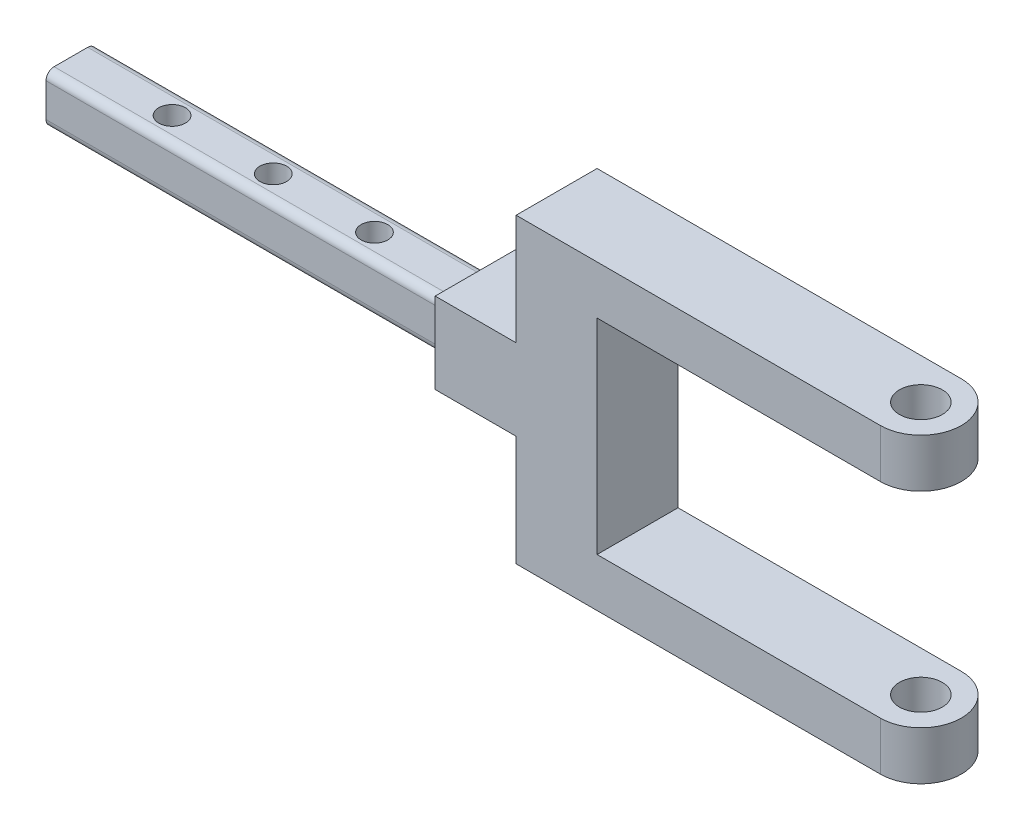
SolidWorks part; units mm, degrees
ref_plane "前视基准面" through (0, 0, 0) normal (0, 0, 1) x (1, 0, 0)
ref_plane "上视基准面" through (0, 0, 0) normal (0, 1, 0) x (1, 0, 0)
ref_plane "右视基准面" through (0, 0, 0) normal (1, 0, 0) x (0, 0, -1)
other "Configuration Table"
sketch "草图1" plane through (0, 0, 0) normal (0, 0, 1) x (1, 0, 0)
  line L0 (0, 12.65) -> (0, -12.65)
  line L1 (0, 12.65) -> (40, 12.65)
  line L2 (40, 12.65) -> (40, 18.65)
  line L3 (40, 18.65) -> (-10, 18.65)
  line L4 (-10, 18.65) -> (-10, -18.65)
  line L5 (-10, -18.65) -> (40, -18.65)
  line L6 (40, -18.65) -> (40, -12.65)
  line L7 (40, -12.65) -> (0, -12.65)
  point P4 (0, 0)
  dimension "D1" = 25.3
  dimension "D2" = 40
  dimension "D3" = 6
  dimension "D4" = 10
extrude "凸台-拉伸1" add sketch "草图1" along normal blind 10
sketch "草图2" plane through (-10, 0, 0) normal (-1, 0, 0) x (0, 0, 1)
  line L0 (8.075, 3.075) -> (8.075, -3.075)
  line L1 (1.925, -3.075) -> (8.075, -3.075)
  line L2 (1.925, 3.075) -> (1.925, -3.075)
  line L3 (1.925, 3.075) -> (8.075, 3.075)
  line L4 (5, 18.65) -> (5, -18.65) construction
  line L5 (0, 0) -> (10, 0) construction
  line L7 (0, 5) -> (10, 5)
  line L8 (0, 18.65) -> (0, -18.65)
  line L9 (0, -18.65) -> (10, -18.65)
  line L10 (10, -18.65) -> (10, 18.65)
  line L11 (10, 18.65) -> (0, 18.65)
  line L12 (0, 18.65) -> (0, -18.65)
  line L13 (0, -18.65) -> (10, -18.65)
  line L14 (10, -18.65) -> (10, 18.65)
  line L15 (10, 18.65) -> (0, 18.65)
  line L16 (0, 5) -> (0, -5)
  line L17 (0, -5) -> (10, -5)
  line L18 (10, 5) -> (10, -5)
  line L19 (5, -5) -> (5, 5) construction
  line L20 (0, 0) -> (10, 0) construction
  line L21 (1.5, 3.5) -> (8.5, 3.5) construction
  line L22 (1.5, 3.5) -> (1.5, -3.5) construction
  line L23 (1.5, -3.5) -> (8.5, -3.5) construction
  line L24 (8.5, 3.5) -> (8.5, -3.5) construction
  line L25 (5, -3.5) -> (5, 3.5) construction
  line L26 (1.5, 0) -> (8.5, 0) construction
  point P6 (5, 0)
  point P13 (5, 0)
  line M8 (0, 18.65) -> (0, -18.65)
  dimension "D2" = 10
  dimension "D3" = 1.5
  dimension "D4" = 6.15
  dimension "D1" = 0
extrude "凸台-拉伸2" add sketch "草图2" along normal blind 10 contours L17 L14 L7 L2 L3 L0 L1 M8 | L3 L2 L1 L0 region at (-10, 0, 5) region at (-10, 4.8586, 5)
extrude "凸台-拉伸3" add sketch "草图2<3>" along normal blind 50 from surface contours L3 L2 L1 L0 region at (-10, 0, 5) starting at face at (-20, 0, 5)
sketch "草图2<3>" plane through (-10, 0, 0) normal (-1, 0, 0) x (0, 0, 1) same geometry as "草图2"
sketch "草图3" plane through (0, 18.65, 0) normal (0, 1, 0) x (1, 0, 0)
  line L0 (-10, -5) -> (40, -5) construction
  line L1 (-10, 0) -> (-10, -10) construction
  line L2 (40, -10) -> (40, 0) construction
  line L3 (40, 0) -> (-10, 0) construction
  circle A0 centre (35, -5) radius 5
  circle A1 centre (35, -5) radius 2.65
  line M1 (40, 0) -> (-10, 0)
  line M3 (-10, -10) -> (40, -10)
  line M4 (40, -10) -> (40, 0)
  dimension "D1" = 5.3
extrude "切除-拉伸1" cut sketch "草图3" against normal through all contours A1 L0 | L0 A1 | A0 M4 M1 | A0 M3 M4 region at (35, 18.65, 6.1247) region at (35, 18.65, 3.8753) region at (38.8832, 18.65, 8.8832) region at (38.8832, 18.65, 1.1168)
sketch "草图4" plane through (0, 3.075, 0) normal (0, 1, 0) x (1, 0, 0)
  line L0 (-20, -5) -> (-70, -5) construction
  line L1 (-20, 0) -> (-20, -10) construction
  line L2 (-70, -8.075) -> (-70, -1.925) construction
  circle A0 centre (-45, -5) radius 1.65
  circle A1 centre (-57.5, -5) radius 1.65
  circle A2 centre (-32.5, -5) radius 1.65
  dimension "D1" = 3.3
  dimension "D2" = 3.3
  dimension "D3" = 3.3
  dimension "D4" = 12.5
  dimension "D5" = 12.5
extrude "切除-拉伸2" cut sketch "草图4" against normal through all
fillet "圆角1" radius 1 4 edges at (-45, 3.075, 8.075) (-45, 3.075, 1.925) (-45, -3.075, 8.075) (-45, -3.075, 1.925)
